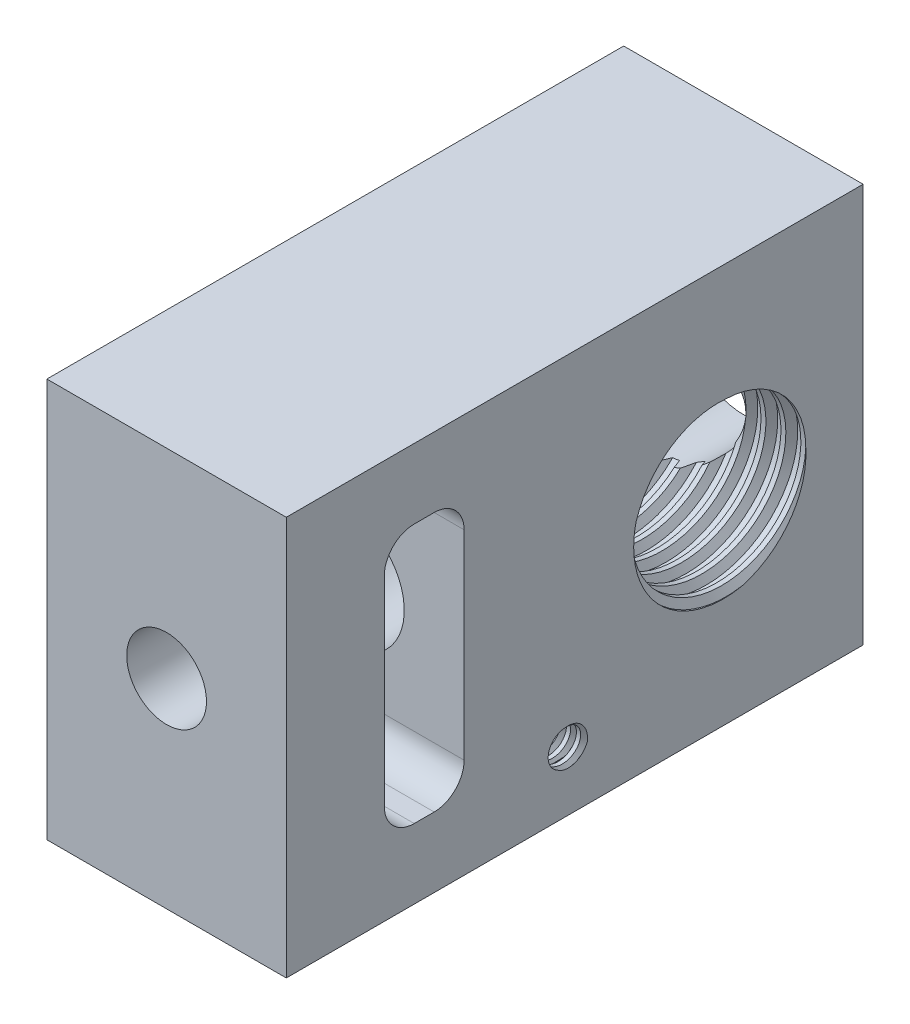
SolidWorks part; units mm, degrees
material "6061-T6 (SS)"
ref_plane "Front Plane" through (0, 0, 0) normal (0, 0, 1) x (1, 0, 0)
ref_plane "Top Plane" through (0, 0, 0) normal (0, 1, 0) x (1, 0, 0)
ref_plane "Right Plane" through (0, 0, 0) normal (1, 0, 0) x (0, 0, -1)
sketch "Sketch1" plane through (0, 0, 0) normal (1, 0, 0) x (0, 0, -1)
  line L0 (-22.9489, 0) -> (11.8364, 0) construction
  line L1 (-22.9489, -15.875) -> (22.9489, -15.875)
  line L2 (-22.9489, -15.875) -> (-22.9489, 15.875)
  line L3 (-22.9489, 15.875) -> (22.9489, 15.875)
  line L4 (22.9489, -15.875) -> (22.9489, 15.875)
  line L5 (-22.9489, -15.875) -> (22.9489, 15.875) construction
  line L6 (-22.9489, 15.875) -> (22.9489, -15.875) construction
  circle A0 centre (11.8364, 0) radius 6.5484
  point P0 (0, 0)
  dimension "D2" = 13.0969
  dimension "D1" = 31.75
  dimension "D3" = 45.8978
  dimension "D4" = 11.1125
extrude "Boss-Extrude1" add sketch "Sketch1" along normal mid plane 19.05
sketch "Sketch2" plane through (0, 0, 22.9489) normal (0, 0, 1) x (1, 0, 0)
  circle A0 centre (0, 0) radius 3.175
  dimension "D1" = 6.35
extrude "Cut-Extrude1" cut sketch "Sketch2" against normal blind 25.4
sketch "Sketch3" plane through (0, 0, -22.9489) normal (0, 0, -1) x (-1, 0, 0)
  circle A0 centre (0, 0) radius 4.7625
  dimension "D1" = 9.525
extrude "Cut-Extrude2" cut sketch "Sketch3" against normal blind 38.1
sketch "Sketch4" plane through (0, 0, 0) normal (0, 1, 0) x (1, 0, 0)
  line L0 (9.525, 18.3848) -> (9.8687, 18.9802)
  line L1 (9.525, 22.9489) -> (9.525, -22.9489) construction
  line L2 (10.3767, 18.9802) -> (10.7204, 18.3848)
  line L3 (10.7204, 18.3848) -> (9.525, 18.3848)
  line L5 (-9.525, 11.8364) -> (9.525, 11.8364) construction
  line L6 (9.525, 5.288) -> (9.525, 18.3848) construction
  line L7 (-9.525, 18.3848) -> (-9.525, 5.288) construction
  line L8 (9.8687, 18.9802) -> (10.3767, 18.9802)
  dimension "D1" = 60
  dimension "D2" = 14.2875
  dimension "D3" = 0.508
sketch "Sketch5" plane through (9.525, 0, 0) normal (1, 0, 0) x (0, 0, -1)
  circle A0 centre (11.8364, 0) radius 6.5484 construction
  circle A1 centre (11.8364, 0) radius 6.5484
curve "Helix/Spiral1" pitch 1.5875 height 25.4 turns 16
sweep "Cut-Sweep1" cut profiles "Sketch4" path "Helix/Spiral1" align with end faces yes
sketch "Sketch6" plane through (0, 0, 0) normal (1, 0, 0) x (0, 0, -1)
  line L0 (-12.7699, 10.3188) -> (-11.1824, 10.3188)
  line L1 (-8.8011, -7.9375) -> (-15.1511, -7.9375) construction
  line L2 (-8.8011, -7.9375) -> (-8.8011, 7.9375)
  line L3 (-8.8011, 7.9375) -> (-15.1511, 7.9375) construction
  line L4 (-15.1511, -7.9375) -> (-15.1511, 7.9375)
  line L5 (-8.8011, -7.9375) -> (-15.1511, 7.9375) construction
  line L6 (-8.8011, 7.9375) -> (-15.1511, -7.9375) construction
  line L7 (22.9489, -15.875) -> (22.9489, 15.875) construction
  line L8 (-11.1824, -10.3187) -> (-12.7699, -10.3188)
  line L9 (-22.9489, -15.875) -> (22.9489, -15.875) construction
  line L10 (-22.9489, 15.875) -> (-22.9489, -15.875) construction
  arc A0 (-15.1511, 7.9375) -> (-12.7699, 10.3188) centre (-12.7699, 7.9375) cw
  arc A1 (-11.1824, 10.3188) -> (-8.8011, 7.9375) centre (-11.1824, 7.9375) cw
  arc A2 (-8.8011, -7.9375) -> (-11.1824, -10.3187) centre (-11.1824, -7.9375) cw
  arc A3 (-12.7699, -10.3188) -> (-15.1511, -7.9375) centre (-12.7699, -7.9375) cw
  circle A4 centre (-0.7239, -11.1125) radius 1.3891
  point P0 (-11.9761, 0)
  dimension "D4" = 2.3813
  dimension "D5" = 2.7781
  dimension "D1" = 15.875
  dimension "D2" = 6.35
  dimension "D3" = 38.1
  dimension "D6" = 4.7625
  dimension "D7" = 22.225
extrude "Cut-Extrude3" cut sketch "Sketch6" against normal through all both and the other way through all
ref_plane "Plane1" through (0, 0, 0.7239) normal (0, 0, 1) x (1, 0, 0)
sketch "Sketch7" plane through (0, 0, 0.7239) normal (0, 0, 1) x (1, 0, 0)
  line L0 (9.525, -9.7234) -> (9.7541, -9.3266)
  line L1 (9.525, 15.875) -> (9.525, -15.875) construction
  line L2 (9.7541, -9.3266) -> (9.9833, -9.7234)
  line L3 (9.9833, -9.7234) -> (9.525, -9.7234)
  line L4 (-9.525, -11.1125) -> (9.525, -11.1125) construction
  line L5 (-9.525, -11.1125) -> (9.525, -11.1125) construction
  line L6 (-9.525, 15.875) -> (-9.525, -15.875) construction
  line L7 (9.525, -12.5016) -> (9.525, -9.7234) construction
  point P11 (0, 0)
  point P14 (0, 0)
  dimension "D1" = 3.5719
  dimension "D2" = 60
sketch "Sketch8" plane through (9.525, 0, 0) normal (1, 0, 0) x (0, 0, -1)
  circle A0 centre (-0.7239, -11.1125) radius 1.3891 construction
  circle A1 centre (-0.7239, -11.1125) radius 1.3891
curve "Helix/Spiral2" pitch 0.7937 height 25.4 turns 32
sweep "Cut-Sweep2" cut profiles "Sketch7" path "Helix/Spiral2" align with end faces yes
